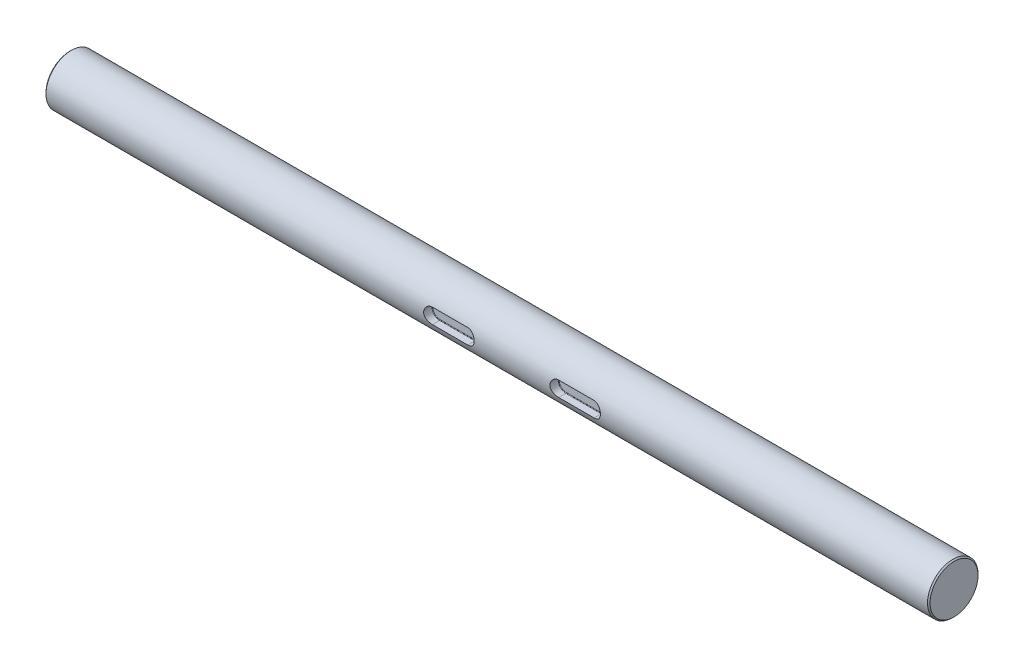
SolidWorks part; units mm, degrees
ref_plane "Front Plane" through (0, 0, 0) normal (0, 0, 1) x (1, 0, 0)
ref_plane "Top Plane" through (0, 0, 0) normal (0, 1, 0) x (1, 0, 0)
ref_plane "Right Plane" through (0, 0, 0) normal (1, 0, 0) x (0, 0, -1)
sketch "Sketch1" plane through (0, 0, 0) normal (0, 0, 1) x (1, 0, 0)
  line L0 (0, 0) -> (350, 0) construction
  line L1 (0, 0) -> (350, 0)
  line L2 (350, 0) -> (350, 10)
  line L3 (350, 10) -> (0, 10)
  line L4 (0, 10) -> (0, 0)
  dimension "L" = 350
  dimension "D" = 20
revolve "Revolve1" add sketch "Sketch1" angle 360 about L0
chamfer "Chamfer1" distance 0.5 angle 45 2 edges at (350, 0, 10) (0, 0, 10)
ref_plane "Plane1" through (0, 0, 10) normal (0, 0, 1) x (1, 0, 0)
ref_plane "Plane2" through (350, 0, 0) normal (1, 0, 0) x (0, 0, -1)
ref_plane "Dim. KA" through (150, 0, 0) normal (1, 0, 0) x (0, 0, -1)
ref_plane "Plane3" through (150, 0, 0) normal (1, 0, 0) x (0, 0, -1)
ref_plane "Plane4" through (170, 0, 0) normal (1, 0, 0) x (0, 0, -1)
sketch "Sketch2" plane through (0, 0, 10) normal (0, 0, 1) x (1, 0, 0)
  line L0 (150, 3) -> (150, -3)
  line L1 (150, 3) -> (170, 3)
  line L2 (150, 3) -> (150, -3) construction
  line L3 (150, -3) -> (170, -3)
  line L4 (170, 3) -> (170, -3) construction
  line L5 (150, -3.3) -> (150, 3.3) construction
  line L6 (150, -3.3) -> (150, 3.3) construction
  line L7 (170, 3) -> (170, -3)
  line L8 (0, 0) -> (170, 0) construction
  line L9 (170, -3.3) -> (170, 3.3) construction
  line L10 (160, 3) -> (160, -3) construction
  dimension "A" = 20
  dimension "B_s" = 6
extrude "Boss-Extrude1" add sketch "Sketch2" against normal blind 3.5 separate body
fillet "Fillet1" 2 edges at (150, 3, 8.25) (150, -3, 8.25) type full round first side face at (160, 3, 8.25) second side face at (160, -3, 8.25) middle face at (150, 0, 8.25)
fillet "Fillet2" 2 edges at (170, 3, 8.25) (170, -3, 8.25) type full round first side face at (161.5, 3, 8.25) second side face at (161.5, -3, 8.25) middle face at (170, 0, 8.25)
sketch "Sketch3" plane through (0, 0, 10) normal (0, 0, 1) x (1, 0, 0)
  line L0 (150, 3) -> (170, 3) construction
  line L1 (167, 3) -> (175, 3)
  line L2 (167, 3) -> (167, -3)
  line L3 (167, -3) -> (175, -3)
  line L4 (175, 3) -> (175, -3)
  line L5 (150, -3) -> (170, -3) construction
  line L6 (172, 3) -> (172, -3) construction
  line L7 (170, 3) -> (170, -3) construction
  line L8 (171, 3) -> (171, -3) construction
  dimension "D1" = 2
  dimension "D2" = 3
  dimension "D3" = 3
extrude "Boss-Extrude2" [suppressed] add sketch "Sketch3" against normal blind 3.5
fillet "Fillet3" radius 0.2 4 edges at (160, 3, 6.5) (150, 0, 6.5) (160, -3, 6.5) (170, 0, 6.5)
other "DeleteFace1" [suppressed]
other "DeleteFace2" [suppressed]
combine bodies "Combine1" operation type subtract main body 101 bodies to subtract 127
ref_plane "KA_SEC1" through (160, 0, 0) normal (1, 0, 0) x (0, 0, -1)
ref_plane "KA_SEC2" through (171, 0, 0) normal (1, 0, 0) x (0, 0, -1)
ref_plane "Plane5" through (200, 0, 0) normal (1, 0, 0) x (0, 0, -1)
ref_plane "Plane6" through (220, 0, 0) normal (1, 0, 0) x (0, 0, -1)
sketch "Sketch4" plane through (0, 0, 10) normal (0, 0, 1) x (1, 0, 0)
  line L0 (150, 3) -> (170, 3) construction
  line L1 (200, 3) -> (220, 3)
  line L2 (200, 3) -> (200, -3) construction
  line L3 (200, -3) -> (220, -3)
  line L4 (220, 3) -> (220, -3) construction
  line L5 (150, -3) -> (170, -3) construction
  line L6 (220, 3) -> (220, -3)
  line L7 (220, -3.3) -> (220, 3.3) construction
  line L8 (200, 3) -> (200, -3)
  line L9 (220, 0) -> (0, 0) construction
  line L10 (200, -4.4) -> (200, 4.4) construction
  line L11 (210, 3) -> (210, -3) construction
  dimension "KB" = 200
  dimension "B" = 20
extrude "Boss-Extrude3" add sketch "Sketch4" against normal blind 3.5 separate body
fillet "Fillet4" 2 edges at (200, 3, 8.25) (200, -3, 8.25) type full round first side face at (210, 3, 8.25) second side face at (210, -3, 8.25) middle face at (200, 0, 8.25)
fillet "Fillet5" 2 edges at (220, 3, 8.25) (220, -3, 8.25) type full round first side face at (211.5, 3, 8.25) second side face at (211.5, -3, 8.25) middle face at (220, 0, 8.25)
sketch "Sketch5" plane through (0, 0, 10) normal (0, 0, 1) x (1, 0, 0)
  line L0 (200, 3) -> (220, 3) construction
  line L1 (217, 3) -> (225, 3)
  line L2 (217, 3) -> (217, -3)
  line L3 (217, -3) -> (225, -3)
  line L4 (225, 3) -> (225, -3)
  line L5 (200, -3) -> (220, -3) construction
  line L6 (222, 3) -> (222, -3) construction
  line L7 (220, 3) -> (220, -3) construction
  line L8 (221, 3) -> (221, -3) construction
  dimension "D1" = 2
  dimension "D2" = 3
  dimension "D3" = 3
extrude "Boss-Extrude4" [suppressed] add sketch "Sketch5" against normal blind 3.5
fillet "Fillet6" radius 0.2 4 edges at (210, -3, 6.5) (220, 0, 6.5) (210, 3, 6.5) (200, 0, 6.5)
other "DeleteFace3" [suppressed]
combine bodies "Combine2" operation type subtract main body 130 bodies to subtract 131
ref_plane "KB_SEC1" through (210, 0, 0) normal (1, 0, 0) x (0, 0, -1)
ref_plane "KB_SEC2" through (221, 0, 0) normal (1, 0, 0) x (0, 0, -1)
ref_plane "Plane7" [suppressed] through (18, 0, 0) normal (1, 0, 0) x (0, 0, -1)
ref_plane "Plane8" [suppressed] through (24, 0, 0) normal (1, 0, 0) x (0, 0, -1)
sketch "Sketch6" [suppressed] plane through (0, 0, 4) normal (0, 0, 1) x (1, 0, 0)
  line L0 (0, 0) -> (24, 0) construction
  line L1 (18, 1.5) -> (24, 1.5)
  line L2 (18, 1.5) -> (18, -1.5) construction
  line L3 (18, -1.5) -> (24, -1.5)
  line L4 (24, 1.5) -> (24, -1.5) construction
  line L5 (1, 1.5) -> (7, 1.5) construction
  line L6 (24, 1.5) -> (24, -1.5)
  line L7 (24, -3.3) -> (24, 3.3) construction
  line L8 (18, 1.5) -> (18, -1.5)
  line L9 (18, -4.4) -> (18, 4.4) construction
  line L10 (21, 1.5) -> (21, -1.5) construction
  dimension "KC" = 18
  dimension "C" = 6
extrude "Boss-Extrude5" [suppressed] add sketch "Sketch6" against normal blind 3.5 separate body
fillet "Fillet7" [suppressed] type full round
fillet "Fillet8" [suppressed] type full round
fillet "Fillet9" [suppressed] radius 0.2
other "DeleteFace4" [suppressed]
combine bodies "Combine3" [suppressed] operation type subtract main body 133 bodies to subtract 135
ref_plane "KC_SEC" [suppressed] through (21, 0, 0) normal (1, 0, 0) x (0, 0, -1)
other "DeleteFace5" [suppressed]
other "DeleteFace6" [suppressed]
chamfer "Chamfer2" [suppressed] distance 2 angle 45
ref_plane "Dim. FC" [suppressed] through (1, 0, 0) normal (1, 0, 0) x (0, 0, -1)
sketch "Sketch7" [suppressed] plane through (0, 0, 0) normal (0, 1, 0) x (1, 0, 0)
  line L0 (0, 0) -> (25, 0) construction
  line L1 (1, -3) -> (2, -3)
  line L2 (1, -3) -> (1, -4)
  line L3 (1, -4) -> (2, -4)
  line L4 (2, -3) -> (2, -4)
  line L5 (1, -3.3) -> (1, 3.3) construction
  line L6 (25, -3.3) -> (25, 3.3) construction
  line L7 (1.5, -3) -> (1.5, -4) construction
  dimension "G" = 1
  dimension "H" = 1
  dimension "D" = 20
extrude "Cut-Extrude1" [suppressed] cut sketch "Sketch7" against normal through all and the other way through all
ref_plane "FC_SEC" [suppressed] through (1.5, 0, 0) normal (1, 0, 0) x (0, 0, -1)
ref_plane "Dim. WFC" [suppressed] through (1, 0, 0) normal (1, 0, 0) x (0, 0, -1)
ref_plane "Dim. W" [suppressed] through (24, 0, 0) normal (1, 0, 0) x (0, 0, -1)
sketch "Sketch8" [suppressed] plane through (0, 0, 0) normal (0, 1, 0) x (1, 0, 0)
  line L0 (0, 0) -> (25, 0) construction
  line L1 (1, -4) -> (2, -4)
  line L2 (1, -4) -> (1, -3)
  line L3 (1, -3) -> (2, -3)
  line L4 (2, -4) -> (2, -3)
  line L5 (1.5, -3) -> (1.5, -4) construction
  line L6 (24, -4) -> (23, -4)
  line L7 (24, -4) -> (24, -3)
  line L8 (24, -3) -> (23, -3)
  line L9 (23, -4) -> (23, -3)
  line L10 (1, -3.3) -> (1, 3.3) construction
  line L11 (24, -3.3) -> (24, 3.3) construction
  line L12 (25, -3.3) -> (25, 3.3) construction
  line L13 (23.5, -3) -> (23.5, -4) construction
  dimension "J" = 1
  dimension "V" = 1
  dimension "H" = 1
  dimension "D" = 20
  dimension "H_R" = 1
extrude "Cut-Extrude2" [suppressed] cut sketch "Sketch8" against normal through all and the other way through all
ref_plane "WFC_SEC1" [suppressed] through (1.5, 0, 0) normal (1, 0, 0) x (0, 0, -1)
ref_plane "WFC_SEC2" [suppressed] through (23.5, 0, 0) normal (1, 0, 0) x (0, 0, -1)
ref_plane "Dim. SFC" [suppressed] through (1, 0, 0) normal (1, 0, 0) x (0, 0, -1)
sketch "Sketch9" [suppressed] plane through (0, 0, 0) normal (0, 1, 0) x (1, 0, 0)
  line L0 (0, 0) -> (2, 0) construction
  line L1 (1, -4) -> (2, -4)
  line L2 (1, -4) -> (1, -3)
  line L3 (1, -3) -> (2, -3)
  line L4 (2, -4) -> (2, -3)
  line L5 (1, -3.3) -> (1, 3.3) construction
  line L7 (1.5, -3) -> (1.5, -4) construction
  dimension "SG" = 1
  dimension "H" = 1
  dimension "D" = 20
extrude "Cut-Extrude3" [suppressed] cut sketch "Sketch9" against normal through all and the other way through all
pattern_circular "CirPattern1" [suppressed] count 2 every 120 of bodies 119
ref_plane "Plane9" [suppressed] through (0, 0, 0) normal (0, -0.5, 0.866) x (1, 0, 0)
sketch "Sketch10" [suppressed] plane through (0, 0, 0) normal (0, -0.5, 0.866) x (1, 0, 0)
  line L0 (0, 0) -> (2, 0) construction
  line L1 (1, -3.3) -> (1, 3.3) construction
  line L2 (1, -3) -> (2, -3)
  line L3 (1, -3) -> (1, -4)
  line L4 (1, -4) -> (2, -4)
  line L5 (2, -3) -> (2, -4)
  dimension "D" = 20
  dimension "SG" = 1
  dimension "H" = 1
ref_plane "SFC_SEC" [suppressed] through (1.5, 0, 0) normal (1, 0, 0) x (0, 0, -1)
sketch "Sketch11" [suppressed] plane through (1.5, 0, 0) normal (1, 0, 0) x (0, 0, -1)
  line L0 (-4, 0) -> (-3, 0) construction
  line L1 (-3, 0) -> (-4, 0) construction
  line L2 (2, -3.4641) -> (1.5, -2.5981) construction
  line L3 (1.5, -2.5981) -> (2, -3.4641) construction
  line L4 (1.5, -2.5981) -> (2, -3.4641) construction
  dimension "ANG" = 120
sketch "Sketch12" [suppressed] plane through (0, 0, 0) normal (0, 1, 0) x (1, 0, 0)
  line L0 (0, 0) -> (25, 0) construction
  line L1 (1.5, -3.5) -> (1.5, -4) construction
  line L2 (0, 3.5) -> (3, 3.5)
  line L3 (0, 3.5) -> (0, 4)
  line L4 (0, 4) -> (3, 4)
  line L5 (3, 3.5) -> (3, 4)
  line L6 (22, 3.5) -> (25, 3.5)
  line L7 (22, 3.5) -> (22, 4)
  line L8 (22, 4) -> (25, 4)
  line L9 (25, 3.5) -> (25, 4)
  line L10 (0, -4) -> (3, -4)
  line L11 (0, -4) -> (0, -3.5)
  line L12 (0, -3.5) -> (3, -3.5)
  line L13 (3, -4) -> (3, -3.5)
  line L14 (22, -4) -> (25, -4)
  line L15 (22, -4) -> (22, -3.5)
  line L16 (22, -3.5) -> (25, -3.5)
  line L17 (25, -4) -> (25, -3.5)
  line L18 (23.5, -3.5) -> (23.5, -4) construction
  dimension "D" = 20
  dimension "KWC_L1" = 3
  dimension "KWC_R1" = 3
  dimension "W_1" = 7
  dimension "W_1_R" = 7
  dimension "KWC" = 3
  dimension "KWC_R2" = 3
extrude "Cut-Extrude4" [suppressed] cut sketch "Sketch12" against normal through all and the other way through all
ref_plane "KWC_SEC1" [suppressed] through (1.5, 0, 0) normal (1, 0, 0) x (0, 0, -1)
ref_plane "KWC_SEC2" [suppressed] through (23.5, 0, 0) normal (1, 0, 0) x (0, 0, -1)
sketch "Sketch13" [suppressed] plane through (0, 0, 0) normal (0, 1, 0) x (1, 0, 0)
  line L0 (0, 0) -> (25, 0) construction
  line L1 (23.5, -3) -> (23.5, -4) construction
  line L2 (0, 3) -> (3, 3)
  line L3 (0, 3) -> (0, 4)
  line L4 (0, 4) -> (3, 4)
  line L5 (3, 3) -> (3, 4)
  line L6 (22, 3) -> (25, 3)
  line L7 (22, 3) -> (22, 4)
  line L8 (22, 4) -> (25, 4)
  line L9 (25, 3) -> (25, 4)
  line L10 (0, -4) -> (3, -4)
  line L11 (0, -4) -> (0, -3)
  line L12 (0, -3) -> (3, -3)
  line L13 (3, -4) -> (3, -3)
  line L14 (22, -4) -> (25, -4)
  line L15 (22, -4) -> (22, -3)
  line L16 (22, -3) -> (25, -3)
  line L17 (25, -4) -> (25, -3)
  line L19 (1.5, -3) -> (1.5, -4) construction
  dimension "D" = 20
  dimension "KWC_L1" = 3
  dimension "KWC_R1" = 3
  dimension "WC" = 6
  dimension "WC_R" = 6
  dimension "KWC" = 3
  dimension "KWC_R2" = 3
extrude "Cut-Extrude5" [suppressed] cut sketch "Sketch13" against normal through all and the other way through all
ref_plane "WC_SEC1" [suppressed] through (1.5, 0, 0) normal (1, 0, 0) x (0, 0, -1)
ref_plane "WC_SEC2" [suppressed] through (23.5, 0, 0) normal (1, 0, 0) x (0, 0, -1)
sketch "Sketch14" [suppressed] plane through (0, 0, 0) normal (0, 0, 1) x (1, 0, 0)
  line L1 (1.1, 3.5) -> (2, 3.5)
  line L2 (1.1, 3.5) -> (1.1, 4)
  line L3 (1.1, 4) -> (2, 4)
  line L4 (2, 3.5) -> (2, 4)
  line L5 (0, 0) -> (2, 0) construction
  line L7 (25, 4) -> (0, 4) construction
  line L8 (0, 4) -> (0, 0) construction
  dimension "D_s_1" = 7
  dimension "M_s" = 0.9
  dimension "TA" = 2
revolve "Cut-Revolve1" [suppressed] cut sketch "Sketch14" angle 360 about L5
sketch "Sketch15" [suppressed] plane through (0, 0, 0) normal (0, 0, 1) x (1, 0, 0)
  line L0 (25, 4) -> (0, 4) construction
  line L1 (23, 3.5) -> (23.9, 3.5)
  line L2 (23, 3.5) -> (23, 4)
  line L3 (23, 4) -> (23.9, 4)
  line L4 (23.9, 3.5) -> (23.9, 4)
  line L5 (0, 0) -> (25, 0) construction
  dimension "D_s_1" = 7
  dimension "M_s" = 0.9
  dimension "TB" = 2
revolve "Cut-Revolve2" [suppressed] cut sketch "Sketch15" angle 360 about L5
sketch "Sketch16" [suppressed] plane through (0, 0, 0) normal (0, 0, 1) x (1, 0, 0)
  line L0 (0, 0) -> (5, 0) construction
  line L1 (0, 4) -> (0, -4) construction
  line L3 (1, 4) -> (5, 4)
  line L4 (1, 4) -> (1, 3.5)
  line L5 (1, 3.5) -> (5, 3.5)
  line L6 (5, 4) -> (5, 3.5)
  line L7 (0, 0) -> (25, 0) construction
  dimension "D_s_2" = 7
  dimension "UC" = 1
  dimension "L1_s" = 4
  dimension "D" = 20
revolve "Cut-Revolve3" [suppressed] cut sketch "Sketch16" angle 360 about L0
ref_plane "Dim. SC" [suppressed] through (2, 0, 0) normal (1, 0, 0) x (0, 0, -1)
sketch "Sketch17" [suppressed] plane through (0, 0, 0) normal (0, 1, 0) x (1, 0, 0)
  line L0 (0, 0) -> (25, 0) construction
  line L1 (2, -3.5) -> (10, -3.5)
  line L2 (2, -3.5) -> (2, -4)
  line L3 (2, -4) -> (10, -4)
  line L4 (10, -3.5) -> (10, -4)
  line L5 (2, 4) -> (10, 4)
  line L6 (2, 4) -> (2, 3.5)
  line L7 (2, 3.5) -> (10, 3.5)
  line L8 (10, 4) -> (10, 3.5)
  line L9 (6, -3.5) -> (6, -4) construction
  line L12 (0, 0) -> (10, 0) construction
  line L14 (2, -3.3) -> (2, 3.3) construction
  dimension "W_2" = 7
  dimension "L2_s" = 8
  dimension "D" = 20
  dimension "L2_s_L1" = 8
extrude "Cut-Extrude6" [suppressed] cut sketch "Sketch17" against normal through all and the other way through all
ref_plane "SC_SEC" [suppressed] through (6, 0, 0) normal (1, 0, 0) x (0, 0, -1)
equation "\"Plane dim\"= \"D@Sketch1\" * 0.5"
equation "\"D1@Plane3\"=if ( \"KA@Dim. KA\" < 1 , 0 , \"KA@Dim. KA\" )"
equation "\"D1@Plane4\"=if ( \"KA@Dim. KA\" > \"L@Sketch1\" - \"A@Sketch2\" - 1 , \"L@Sketch1\" , \"KA@Dim. KA\" + \"A@Sketch2\" )"
equation "\"D1@Plane6\"=if ( \"KB@Sketch4\" > \"L@Sketch1\" - \"B@Sketch4\" - 1 , \"L@Sketch1\" , \"KB@Sketch4\" + \"B@Sketch4\" )"
equation "\"D1@Plane8\"=if ( \"KC@Sketch6\" > \"L@Sketch1\" - \"C@Sketch6\" - 1 , \"L@Sketch1\" , \"KC@Sketch6\" + \"C@Sketch6\" )"
equation "\"D1@Plane5\"= if ( \"KB@Sketch4\" - \"KA@Dim. KA\" - \"A@Sketch2\" < 2 , ( \"KA@Dim. KA\" + \"A@Sketch2\" ) - ( \"B_s@Sketch2\" / 2 ) - 1 , \"KB@Sketch4\" )"
equation "\"D1@Plane7\"=if(\"KC@Sketch6\"-\"KB@Sketch4\"-\"B@Sketch4\"<2,(\"KB@Sketch4\"+\"B@Sketch4\")-(\"B_s@Sketch2\"/2)-1,\"KC@Sketch6\")"
equation "\"D@Sketch10\" = \"D@Sketch9\""
equation "\"SG@Sketch10\" = \"SG@Sketch9\""
equation "\"H@Sketch10\"= \"H@Sketch9\""
equation "\"D3@Sketch3\"= \"B_s@Sketch2\" / 2"
equation "\"D2@Sketch3\" = \"B_s@Sketch2\" / 2"
equation "\"D2@Sketch5\" = \"B_s@Sketch2\" / 2"
equation "\"D3@Sketch5\"= \"B_s@Sketch2\" / 2"
